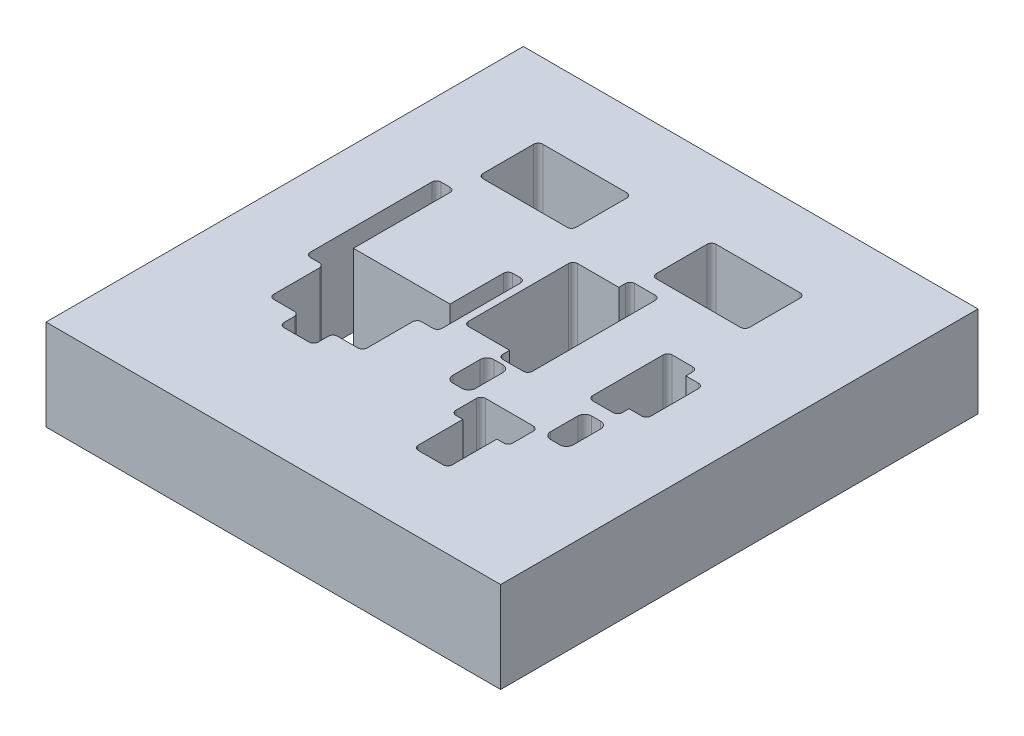
SolidWorks part; units mm, degrees
material "K110"
ref_plane "Front Plane" through (0, 0, 0) normal (0, 0, 1) x (1, 0, 0)
ref_plane "Top Plane" through (0, 0, 0) normal (0, 1, 0) x (1, 0, 0)
ref_plane "Right Plane" through (0, 0, 0) normal (1, 0, 0) x (0, 0, -1)
sketch "Sketch1" plane through (0, 0, 0) normal (0, 1, 0) x (1, 0, 0)
  line L1 (-100, -105) -> (100, -105)
  line L2 (-100, -105) -> (-100, 105)
  line L3 (-100, 105) -> (100, 105)
  line L4 (100, -105) -> (100, 105)
  line L5 (-100, -105) -> (100, 105) construction
  line L6 (-100, 105) -> (100, -105) construction
  point P0 (0, 0)
  dimension "D1" = 210
  dimension "D2" = 200
extrude "Boss-Extrude1" add sketch "Sketch1" along normal blind 40
sketch "Sketch2" plane through (0, 40, 0) normal (0, 1, 0) x (1, 0, 0)
  line L0 (17.25, 55.73) -> (55.25, 55.73) construction
  line L1 (15.75, 32.73) -> (15.75, -12.27) construction
  line L2 (58.25, 13.73) -> (58.25, -8.27) construction
  line L3 (30.25, -47.4) -> (42.25, -47.4) construction
  line L4 (17.25, 55.73) -> (55.25, 55.73)
  line L5 (15.75, 32.73) -> (15.75, -12.27)
  line L6 (58.25, 13.73) -> (58.25, -8.27)
  line L7 (30.25, -47.4) -> (42.25, -47.4)
sketch "Sketch3" plane through (0, 40, 0) normal (0, 1, 0) x (1, 0, 0)
  line L0 (30.25, -47.4) -> (42.25, -47.4) construction
  line L1 (28.75, -72.03) -> (43.75, -72.03)
  line L2 (28.75, -72.03) -> (28.75, -50.4)
  line L3 (23.75, -37.4) -> (48.75, -37.4)
  line L4 (43.75, -72.03) -> (43.75, -50.4)
  line L8 (36.25, -37.4) -> (36.25, -72.03) construction
  line L9 (36.25, 69.53) -> (36.25, -69.53) construction
  line L11 (43.75, -50.4) -> (48.75, -50.4)
  line L12 (48.75, -50.4) -> (48.75, -37.4)
  line L13 (28.75, -50.4) -> (23.75, -50.4)
  line L14 (23.75, -50.4) -> (23.75, -37.4)
  line L15 (66.38, -69.53) -> (-4.87, -69.53) construction
  dimension "D1" = 10
  dimension "D2" = 15
  dimension "D3" = 3
  dimension "D4" = 25
  dimension "D5" = 2.5
extrude "Cut-Extrude2" cut sketch "Sketch3" against normal up to next contours L3 L12 L11 L4 L1 L2 L13 L14
fillet "Fillet3" radius 2 6 edges at (43.75, 20, 72.03) (28.75, 20, 72.03) (48.75, 20, 50.4) (23.75, 20, 50.4) (48.75, 20, 37.4) (23.75, 20, 37.4)
sketch "Sketch4" plane through (0, 40, 0) normal (0, 1, 0) x (1, 0, 0)
  line L0 (48.25, -14.77) -> (61.25, -14.77)
  line L5 (61.25, -14.77) -> (61.25, -9.77)
  line L6 (64.38, 13.73) -> (58.25, 13.73) construction
  line L7 (66.38, 69.53) -> (66.38, -69.53) construction
  line L8 (66.38, 2.73) -> (51.7072, 2.73) construction
  line L9 (66.38, -6.27) -> (66.38, 11.73) construction
  line L10 (61.25, -9.77) -> (68.88, -9.77)
  line L11 (68.88, -9.77) -> (68.88, 15.23)
  line L13 (68.88, 15.23) -> (61.25, 15.23)
  line L14 (61.25, 15.23) -> (61.25, 20.23)
  line L15 (61.25, 20.23) -> (48.25, 20.23)
  line L16 (48.25, 20.23) -> (48.25, -14.77)
  line L17 (58.25, 13.73) -> (58.25, -8.27) construction
  dimension "D1" = 1.5
  dimension "D2" = 5
  dimension "D3" = 2.5
  dimension "D4" = 10
  dimension "D5" = 3
extrude "Cut-Extrude3" cut sketch "Sketch4" against normal up to next
fillet "Fillet4" radius 2 6 edges at (68.88, 20, 9.77) (68.88, 20, -15.23) (61.25, 20, -20.23) (48.25, 20, -20.23) (48.25, 20, 14.77) (61.25, 20, 14.77)
sketch "Sketch5" plane through (0, 40, 0) normal (0, 1, 0) x (1, 0, 0)
  line L0 (-7.37, -13.77) -> (12.75, -13.77)
  line L2 (12.75, -18.77) -> (25.75, -18.77)
  line L3 (25.75, -18.77) -> (25.75, 39.23)
  line L4 (25.75, 39.23) -> (12.75, 39.23)
  line L5 (12.75, 39.23) -> (12.75, 34.23)
  line L6 (12.75, 34.23) -> (-7.37, 34.23)
  line L7 (-7.37, 34.23) -> (-7.37, -13.77)
  line L8 (15.75, 32.73) -> (15.75, -12.27) construction
  line L9 (-4.87, 69.53) -> (-4.87, -69.53) construction
  line L10 (-4.87, 10.23) -> (25.75, 10.23) construction
  line L11 (-4.87, 26.73) -> (-4.87, -6.27) construction
  line L12 (12.75, -18.77) -> (12.75, -13.77)
  line L13 (1.13, -12.27) -> (15.75, -12.27) construction
  line L17 (-18, -8.27) -> (-18, 13.73) construction
  line L18 (-18, 2.73) -> (-15, 2.73) construction
  dimension "D1" = 3
  dimension "D2" = 10
  dimension "D3" = 2.5
  dimension "D4" = 1.5
  dimension "D5" = 5
extrude "Cut-Extrude4" cut sketch "Sketch5" against normal up to next
fillet "Fillet5" radius 2 6 edges at (25.75, 20, -39.23) (12.75, 20, 18.77) (25.75, 20, 18.77) (-7.37, 20, 13.77) (12.75, 20, -39.23) (-7.37, 20, -34.23)
sketch "Sketch6" plane through (0, 40, 0) normal (0, 1, 0) x (1, 0, 0)
  line L0 (15.75, 72.03) -> (15.75, 45.73)
  line L3 (15.75, 45.73) -> (56.75, 45.73)
  line L6 (56.75, 45.73) -> (56.75, 72.03)
  line L7 (56.75, 72.03) -> (15.75, 72.03)
  line L8 (36.25, 69.53) -> (36.25, 45.73) construction
  line L9 (36.25, 69.53) -> (36.25, -69.53) construction
  line L10 (66.38, 69.53) -> (-4.87, 69.53) construction
  line L12 (17.25, 55.73) -> (55.25, 55.73) construction
  dimension "D1" = 2.5
  dimension "D2" = 41
  dimension "D5" = 10
extrude "Cut-Extrude5" cut sketch "Sketch6" against normal up to next
fillet "Fillet6" radius 2 4 edges at (15.75, 20, -72.03) (56.75, 20, -72.03) (15.75, 20, -45.73) (56.75, 20, -45.73)
sketch "Sketch7" plane through (0, 40, 0) normal (0, 1, 0) x (1, 0, 0)
  line L0 (57.75, -29.77) -> (57.75, -32.27) construction
  line L3 (60.25, -29.77) -> (55.25, -29.77) construction
  line L4 (60.25, -27.27) -> (60.25, -32.27) construction
  line L5 (55.25, -11.27) -> (55.25, -38.4) construction
  line L7 (59.75, -20.77) -> (55.75, -20.77)
  line L8 (62.75, -23.77) -> (62.75, -35.77)
  line L9 (59.75, -38.77) -> (55.75, -38.77)
  line L10 (52.75, -23.77) -> (52.75, -35.77)
  arc A2 (55.75, -38.77) -> (52.75, -35.77) centre (55.75, -35.77) cw
  arc A3 (62.75, -35.77) -> (59.75, -38.77) centre (59.75, -35.77) cw
  arc A4 (59.75, -20.77) -> (62.75, -23.77) centre (59.75, -23.77) cw
  arc A5 (55.75, -20.77) -> (52.75, -23.77) centre (55.75, -23.77) ccw
  point P14 (52.75, -38.77)
  point P17 (62.75, -38.77)
  point P20 (62.75, -20.77)
  dimension "D4" = 3
  dimension "D1" = 2.5
  dimension "D2" = 18
  dimension "D3" = 10
  dimension "D5" = 9
extrude "Cut-Extrude6" cut sketch "Sketch7" against normal up to next
sketch "Sketch8" plane through (0, 40, 0) normal (0, 1, 0) x (1, 0, 0)
  line L0 (12.25, -29.77) -> (17.25, -29.77) construction
  line L3 (12.25, -32.27) -> (12.25, -27.27) construction
  line L4 (59.75, -20.77) -> (55.75, -20.77) construction
  line L7 (17.25, -38.4) -> (17.25, -13.77) construction
  line L8 (14.75, -29.77) -> (14.75, -32.27) construction
  line L9 (55.75, -38.77) -> (59.75, -38.77) construction
  line L10 (12.75, -20.77) -> (16.75, -20.77)
  line L11 (9.75, -23.77) -> (9.75, -35.77)
  line L12 (12.75, -38.77) -> (16.75, -38.77)
  line L13 (19.75, -23.77) -> (19.75, -35.77)
  arc A2 (9.75, -35.77) -> (12.75, -38.77) centre (12.75, -35.77) ccw
  arc A3 (16.75, -38.77) -> (19.75, -35.77) centre (16.75, -35.77) ccw
  arc A4 (16.75, -20.77) -> (19.75, -23.77) centre (16.75, -23.77) cw
  arc A5 (12.75, -20.77) -> (9.75, -23.77) centre (12.75, -23.77) ccw
  dimension "D1" = 2.5
  dimension "D2" = 3
extrude "Cut-Extrude7" cut sketch "Sketch8" against normal up to next
ref_plane "Plane1" through (0, 0, 29.77) normal (0, 0, 1) x (1, 0, 0)
sketch "Sketch9" plane through (0, 0, 29.77) normal (0, 0, 1) x (1, 0, 0)
  line L0 (62.75, 30) -> (63.2737, 0)
  line L1 (62.75, 0) -> (62.75, 40) construction
  line L2 (61.25, 0) -> (66.88, 0) construction
  line L3 (63.2737, 0) -> (62.75, 0)
  line L4 (62.75, 0) -> (62.75, 30)
  line L5 (100, 40) -> (-100, 40) construction
  dimension "D1" = 10
  dimension "D2" = 1
sketch "Sketch10" plane through (0, 40, 0) normal (0, 1, 0) x (1, 0, 0)
  line L0 (59.75, -20.77) -> (55.75, -20.77) construction
  line L1 (52.75, -23.77) -> (52.75, -35.77) construction
  line L2 (55.75, -38.77) -> (59.75, -38.77) construction
  line L3 (62.75, -35.77) -> (62.75, -23.77) construction
  line L4 (59.75, -20.77) -> (55.75, -20.77)
  line L5 (52.75, -23.77) -> (52.75, -35.77)
  line L6 (55.75, -38.77) -> (59.75, -38.77)
  line L7 (62.75, -35.77) -> (62.75, -23.77)
  arc A0 (62.75, -23.77) -> (59.75, -20.77) centre (59.75, -23.77) ccw construction
  arc A1 (55.75, -20.77) -> (52.75, -23.77) centre (55.75, -23.77) ccw construction
  arc A2 (52.75, -35.77) -> (55.75, -38.77) centre (55.75, -35.77) ccw construction
  arc A3 (59.75, -38.77) -> (62.75, -35.77) centre (59.75, -35.77) ccw construction
  arc A4 (62.75, -23.77) -> (59.75, -20.77) centre (59.75, -23.77) ccw
  arc A5 (55.75, -20.77) -> (52.75, -23.77) centre (55.75, -23.77) ccw
  arc A6 (52.75, -35.77) -> (55.75, -38.77) centre (55.75, -35.77) ccw
  arc A7 (59.75, -38.77) -> (62.75, -35.77) centre (59.75, -35.77) ccw
sweep "Cut-Sweep1" cut profiles "Sketch9" path "Sketch10"
sketch "Sketch12" plane through (0, 0, 29.77) normal (0, 0, 1) x (1, 0, 0)
  line L0 (19.75, 30) -> (20.2737, 0)
  line L1 (19.75, 0) -> (19.75, 40) construction
  line L2 (14.75, 0) -> (23.75, 0) construction
  line L3 (20.2737, 0) -> (19.75, 0)
  line L4 (19.75, 0) -> (19.75, 30)
  line L5 (100, 40) -> (-100, 40) construction
  dimension "D1" = 10
  dimension "D2" = 1
sketch "Sketch14" plane through (0, 40, 0) normal (0, 1, 0) x (1, 0, 0)
  line L0 (12.75, -38.77) -> (16.75, -38.77) construction
  line L1 (19.75, -35.77) -> (19.75, -23.77) construction
  line L2 (9.75, -23.77) -> (9.75, -35.77) construction
  line L3 (16.75, -20.77) -> (12.75, -20.77) construction
  line L4 (12.75, -38.77) -> (16.75, -38.77)
  line L5 (19.75, -35.77) -> (19.75, -23.77)
  line L6 (9.75, -23.77) -> (9.75, -35.77)
  line L7 (16.75, -20.77) -> (12.75, -20.77)
  arc A0 (9.75, -35.77) -> (12.75, -38.77) centre (12.75, -35.77) ccw construction
  arc A1 (16.75, -38.77) -> (19.75, -35.77) centre (16.75, -35.77) ccw construction
  arc A2 (12.75, -20.77) -> (9.75, -23.77) centre (12.75, -23.77) ccw construction
  arc A3 (19.75, -23.77) -> (16.75, -20.77) centre (16.75, -23.77) ccw construction
  arc A4 (9.75, -35.77) -> (12.75, -38.77) centre (12.75, -35.77) ccw
  arc A5 (16.75, -38.77) -> (19.75, -35.77) centre (16.75, -35.77) ccw
  arc A6 (12.75, -20.77) -> (9.75, -23.77) centre (12.75, -23.77) ccw
  arc A7 (19.75, -23.77) -> (16.75, -20.77) centre (16.75, -23.77) ccw
sweep "Cut-Sweep2" cut profiles "Sketch12" path "Sketch14"
pattern_linear "LPattern1" count 2 spacing 76.25 along (-1, 0, 0) of "Cut-Extrude5"
fillet "Fillet9" radius 2 4 edges at (-60.5, 20, -45.73) (-19.5, 20, -45.73) (-19.5, 20, -72.03) (-60.5, 20, -72.03)
sketch "Sketch19" plane through (0, 40, 0) normal (0, 1, 0) x (1, 0, 0)
  line L0 (-47.5, -54.77) -> (-32.5, -54.77)
  line L1 (-32.5, -54.77) -> (-32.5, -46.27)
  line L2 (-32.5, -46.27) -> (-19.5, -46.27)
  line L3 (-19.5, -46.27) -> (-19.5, -22.27)
  line L4 (-19.5, -22.27) -> (-10.5, -22.27)
  line L5 (-10.5, -22.27) -> (-10.5, 16.23)
  line L6 (-18, -9.27) -> (-60.5, -9.27)
  line L7 (-68.5, 35.23) -> (-68.5, -22.27)
  line L8 (-68.5, -22.27) -> (-60.5, -22.27)
  line L9 (-60.5, -22.27) -> (-60.5, -46.27)
  line L10 (-60.5, -46.27) -> (-47.5, -46.27)
  line L11 (-47.5, -46.27) -> (-47.5, -54.77)
  line L12 (-40, -19.27) -> (-40, -9.27) construction
  line L13 (-59, -19.27) -> (-21, -19.27) construction
  line L14 (-21, -11.27) -> (-21, -19.27) construction
  line L15 (-18, -8.27) -> (-18, 13.73) construction
  line L17 (-60.5, -9.27) -> (-60.5, 35.23)
  line L18 (-60.5, 35.23) -> (-68.5, 35.23)
  line L19 (-60.5, -12.27) -> (-60.5, 32.73) construction
  line L20 (-60.5, 32.73) -> (-66.5, 32.73) construction
  line L21 (-18, -9.27) -> (-18, 16.23)
  line L22 (-18, 16.23) -> (-10.5, 16.23)
  dimension "D1" = 10
  dimension "D2" = 3
  dimension "D3" = 9
  dimension "D4" = 1.5
  dimension "D5" = 1.5
  dimension "D6" = 8.5
  dimension "D7" = 24
  dimension "D8" = 8
  dimension "D9" = 0
  dimension "D10" = 2.5
  dimension "D11" = 2.5
  dimension "D12" = 0
extrude "Cut-Extrude10" cut sketch "Sketch19" against normal up to next
fillet "Fillet10" radius 2 14 edges at (-32.5, 20, 46.27) (-47.5, 20, 46.27) (-60.5, 20, 22.27) (-19.5, 20, 22.27) (-60.5, 20, 46.27) (-47.5, 20, 54.77) (-32.5, 20, 54.77) (-19.5, 20, 46.27) (-10.5, 20, 22.27) (-68.5, 20, 22.27) (-18, 20, -16.23) (-10.5, 20, -16.23) (-60.5, 20, -35.23) (-68.5, 20, -35.23)
